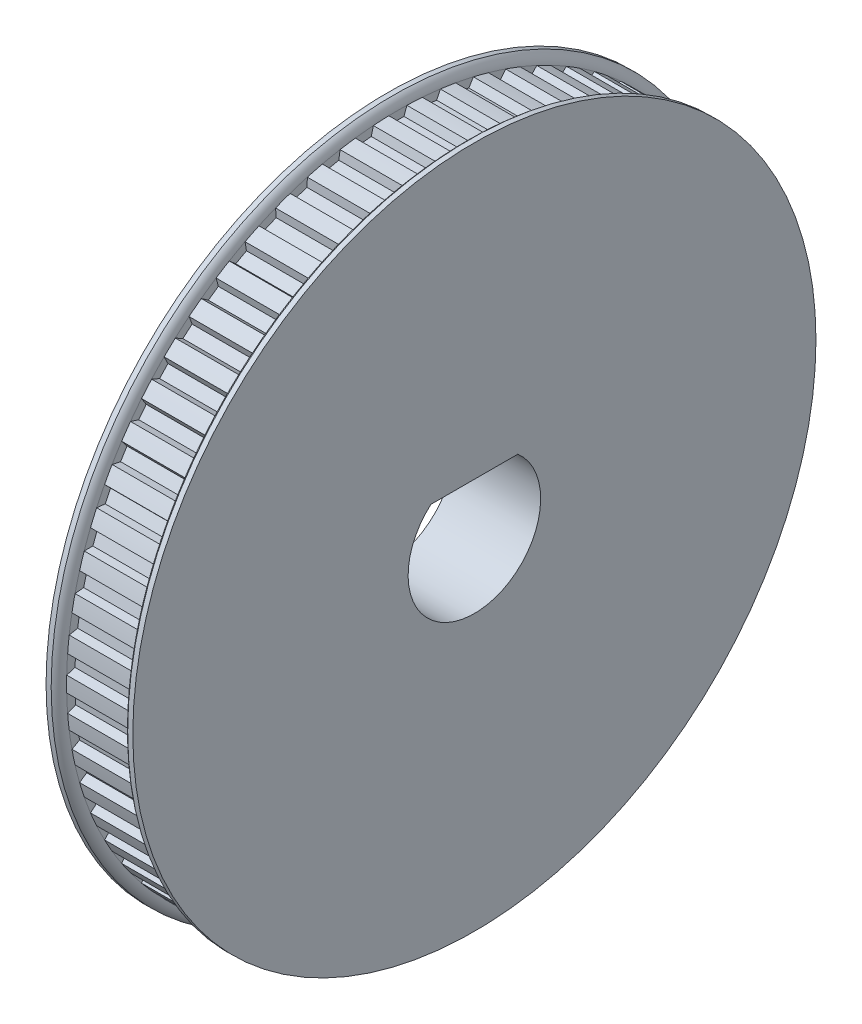
SolidWorks part; units mm, degrees
ref_plane "Front Plane" through (0, 0, 0) normal (0, 0, 1) x (1, 0, 0)
ref_plane "Top Plane" through (0, 0, 0) normal (0, 1, 0) x (1, 0, 0)
ref_plane "Right Plane" through (0, 0, 0) normal (1, 0, 0) x (0, 0, -1)
sketch "Sketch1" plane through (0, 0, 0) normal (1, 0, 0) x (0, 0, -1)
  line L3 (0, 0) -> (0, 51.285) construction
  line L6 (0, 51.285) -> (0, 52.485) construction
  line L7 (-1.325, 52.4683) -> (-0.8915, 51.2773)
  line L8 (1.325, 52.4683) -> (0.8915, 51.2773)
  line L9 (0, -2.2) -> (0, -3.2) construction
  line L10 (0, 52.985) -> (0, 52.485) construction
  line L12 (-0.8915, 51.2773) -> (0.8915, 51.2773)
  line L15 (0, 0) -> (0, -2.2) construction
  circle A0 centre (0, 0) radius 52.985 construction
  circle A1 centre (0, 0) radius 51.285 construction
  arc A7 (1.325, 52.4683) -> (-1.325, 52.4683) centre (0, 0) ccw
  dimension "PD" = 105.97
  dimension "D1" = 40
  dimension "D3" = 0.5
  dimension "D2" = 1.2
  dimension "D4" = 2.65
sketch "Sketch2" plane through (0, 0, 0) normal (0, 0, 1) x (1, 0, 0)
  line L0 (-10.5, 0) -> (10.5, 0) construction
  line L1 (-10.5, 4) -> (10.5, 4) construction
  line L2 (-10.5, 4) -> (-10.5, 19) construction
  line L3 (-2.2, 54) -> (-1.45, 54)
  line L4 (-0.7, 52.485) -> (-2.2, 52.485) construction
  line L5 (9.75, 52.485) -> (9.75, 54) construction
  line L6 (-0.7, 52.485) -> (9, 52.485)
  line L7 (-2.2, 19) -> (-2.2, 4)
  line L8 (9, 52.485) -> (10.5, 52.485) construction
  line L9 (9.75, 54) -> (10.5, 54)
  line L10 (10.5, 54) -> (10.5, 4)
  line L11 (-2.2, 4) -> (10.5, 4)
  line L12 (-6.35, 19) -> (-6.35, 4) construction
  line L13 (-2.2, 54) -> (-2.2, 19)
  line L14 (-2.2, 19) -> (-10.5, 19) construction
  arc A0 (9, 52.485) -> (9.75, 54) centre (10.9052, 52.485) cw
  arc A1 (-0.7, 52.485) -> (-1.45, 54) centre (-2.6052, 52.485) ccw
  point P19 (-0.7, 52.485)
  point P20 (9, 52.485)
  dimension "Bore Size" = 4
  dimension "Overall Width" = 21
  dimension "Inside Width" = 9.7
  dimension "Outside Width" = 12.7
  dimension "Hub Dia" = 19
  dimension "OD" = 108
sketch "Sketch6" plane through (0, 0, 0) normal (0, 0, 1) x (1, 0, 0)
  line L0 (9.75, 54) -> (10.5, 54) construction
  line L1 (-0.7, 52.485) -> (9, 52.485) construction
  line L2 (-2.2, 54) -> (-1.45, 54) construction
  line L3 (-2.2, 54) -> (-2.2, 19) construction
  line L4 (-2.2, 19) -> (-10.5, 19) construction
  line L5 (-10.5, 4) -> (-10.5, 19) construction
  line L6 (-10.5, 4) -> (10.5, 4) construction
  line L7 (10.5, 54) -> (10.5, 4) construction
  line L8 (9.75, 54) -> (10.5, 54)
  line L9 (-0.7, 52.485) -> (9, 52.485)
  line L10 (-2.2, 54) -> (-1.45, 54)
  line L11 (-2.2, 54) -> (-2.2, 19)
  line L12 (-2.2, 19) -> (-10.5, 19)
  line L13 (-10.5, 4) -> (-10.5, 19)
  line L14 (-10.5, 4) -> (10.5, 4)
  line L15 (10.5, 54) -> (10.5, 4)
  line L16 (-2.2, 19) -> (-2.2, 4)
  arc A0 (9.75, 54) -> (9, 52.485) centre (10.9052, 52.485) ccw construction
  arc A1 (-0.7, 52.485) -> (-1.45, 54) centre (-2.6052, 52.485) ccw construction
  arc A2 (9.75, 54) -> (9, 52.485) centre (10.9052, 52.485) ccw
  arc A3 (-0.7, 52.485) -> (-1.45, 54) centre (-2.6052, 52.485) ccw
revolve "Revolve1" add sketch "Sketch6" angle 360 about L14 region at (4.15, 28.3978, 0)
sketch "Sketch3" plane through (0, 0, 0) normal (1, 0, 0) x (0, 0, -1)
  line L2 (-1.325, 52.4683) -> (-0.8915, 51.2773) construction
  line L3 (-0.8915, 51.2773) -> (0.8915, 51.2773) construction
  line L4 (1.325, 52.4683) -> (0.8915, 51.2773) construction
  line L5 (-1.325, 52.4683) -> (-0.8915, 51.2773)
  line L6 (-0.8915, 51.2773) -> (0.8915, 51.2773)
  line L7 (1.325, 52.4683) -> (0.8915, 51.2773)
  arc A1 (1.325, 52.4683) -> (-1.325, 52.4683) centre (0, 0) ccw construction
  arc A2 (1.325, 52.4683) -> (-1.325, 52.4683) centre (0, 0) ccw
extrude "Cut-Extrude1" cut sketch "Sketch3" along normal up to vertex (9 mm away) from vertex up to point (9, 52.485, 0) starting at point (-0.7, 52.485, 0)
pattern_circular "CirPattern1" count 62 over 360 about axis through (-10.5, 4, 0) along (-1, 0, 0) of "Cut-Extrude1"
sketch "Sketch5" plane through (0, 0, 0) normal (0, 0, 1) x (1, 0, 0)
  line L0 (-10.5, 0) -> (10.5, 0) construction
  point P0 (9, 0)
sketch "Sketch8" plane through (-2.2, 0, 0) normal (-1, 0, 0) x (0, 0, 1)
  line L0 (-6.3617, 11.3225) -> (6.3617, 11.3225)
  arc A0 (-6.3617, 11.3225) -> (6.3617, 11.3225) centre (0, 4) ccw
  circle A1 centre (0, 4) radius 50 construction
  dimension "D1" = 19.4
  dimension "D2" = 7.3225
extrude "Cut-Extrude2" cut sketch "Sketch8" against normal through all
equation "\"D3@Sketch1\" = \"ht@Sketch1\" / 2"
equation "\"D2@Sketch1\" = \"hs@Sketch1\" - \"ht@Sketch1\""
